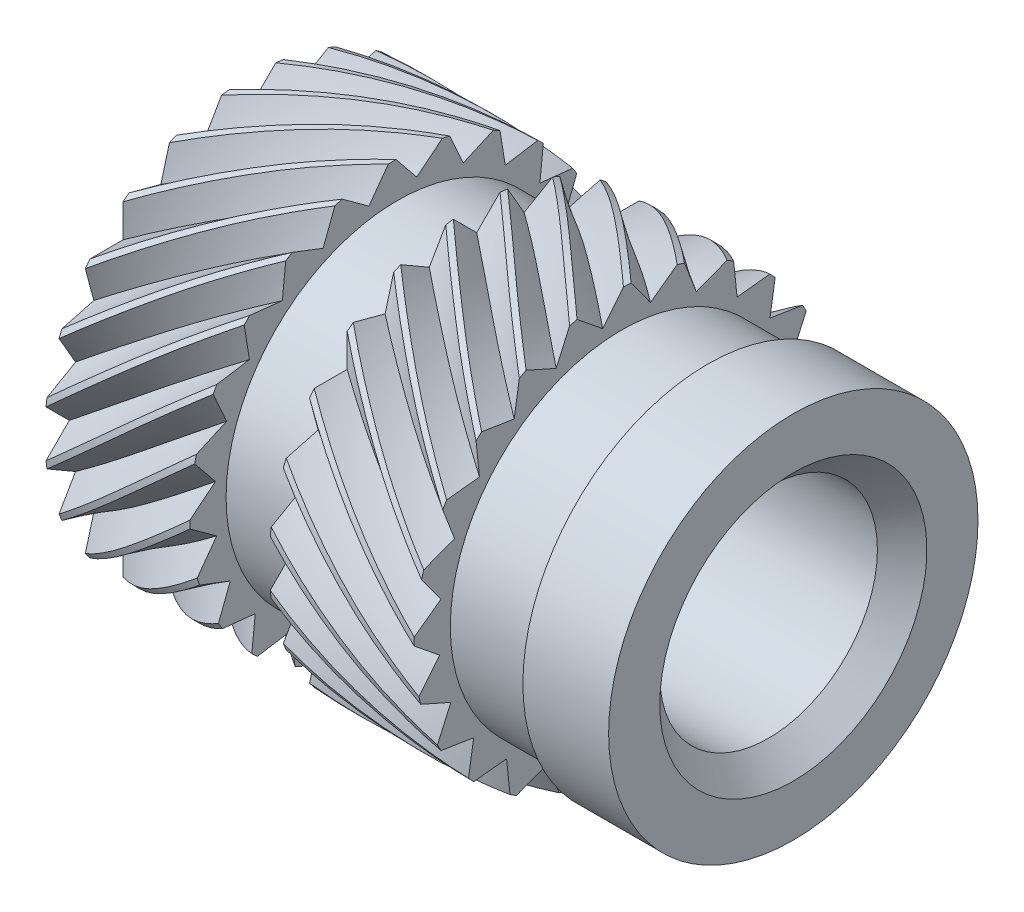
SolidWorks part; units mm, degrees
material "ЛС59-1 ГОСТ 15527-2004"
ref_plane "Front" through (0, 0, 0) normal (0, 0, 1) x (1, 0, 0)
ref_plane "Top" through (0, 0, 0) normal (0, 1, 0) x (1, 0, 0)
ref_plane "Right" through (0, 0, 0) normal (1, 0, 0) x (0, 0, -1)
sketch "Эскиз1" plane through (0, 0, 0) normal (0, 0, 1) x (1, 0, 0)
  line L0 (0, 1.5) -> (0, 3.15)
  line L1 (0, 3.15) -> (2.2, 3.15)
  line L2 (2.2, 3.15) -> (2.2, 2.6)
  line L3 (2.2, 2.6) -> (3.4, 2.6)
  line L4 (3.4, 2.6) -> (3.4, 3.15)
  line L5 (3.4, 3.15) -> (5.6, 3.15)
  line L6 (5.6, 3.15) -> (5.6, 2.6)
  line L7 (5.6, 2.6) -> (6.9, 2.6)
  line L8 (6.9, 2.6) -> (6.9, 2.8)
  line L9 (6.9, 2.8) -> (8.2, 2.8)
  line L10 (8.2, 2.8) -> (8.2, 1.5)
  line L11 (8.2, 1.5) -> (0, 1.5)
  line L12 (0, 0) -> (5.7184, 0) construction
  dimension "D1" = 6.3
  dimension "D2" = 3
  dimension "D3" = 5.2
  dimension "D4" = 5.2
  dimension "D5" = 5.6
  dimension "D6" = 8.2
  dimension "D7" = 1.3
  dimension "D8" = 1.3
  dimension "D9" = 2.2
revolve "Повернуть1" add sketch "Эскиз1" angle 360 about L12
hole_wizard "Отверстие обработанное метчиком M41" positions "Эскиз3" profile "Эскиз2" tap size "M4" standard "Din" end condition through all
sketch "Эскиз3" plane through (0, 0, 0) normal (-1, 0, 0) x (0, 0, 1)
  point P0 (0, 0)
sketch "Эскиз2" plane through (0, 0, 0) normal (0, 1, 0) x (0, 0, 1)
  line L0 (0, 0) -> (0, 8.2)
  line L1 (0, 8.2) -> (2.025, 8.2)
  line L2 (1.65, 7.825) -> (1.65, 0.375)
  line L3 (1.65, 0.375) -> (2.025, 0)
  line L5 (2.025, 0) -> (0, 0)
  line L6 (-1.65, 0.375) -> (-2.025, 0) construction
  line L7 (2.025, 8.2) -> (1.65, 7.825)
  line L8 (-2.025, 8.2) -> (-1.65, 7.825) construction
  line L11 (0, -6.35) -> (0, 107.95) construction
  dimension "Диаметр проходного сверла" = 3.3
  dimension "Глубина проходного сверла" = 8.2
  dimension "Диаметр передней зенковки" = 4.05
  dimension "Угол передней зенковки" = 90
  dimension "Диаметр задней зенковки" = 4.05
  dimension "Угол задней зенковки" = 90
cosmetic thread "Отверстие резьбы1" parameters "D2"=4
sketch "Эскиз4" plane through (0, 0, 0) normal (-1, 0, 0) x (0, 0, 1)
  circle A1 centre (0, 0) radius 3.15
  circle A2 centre (0, 0) radius 3.15
  dimension "D1" = 0
curve "Спираль1" pitch 22 height 2.86 turns 0.13
sketch "Эскиз5" plane through (0, 0, 0) normal (-1, 0, 0) x (0, 0, 1)
  line L0 (3.1301, 0.3536) -> (2.7765, 0)
  line L1 (2.7765, 0) -> (3.1301, -0.3536)
  line L2 (0, 0) -> (2.7765, 0) construction
  circle A0 centre (0, 0) radius 3.15 construction
  arc A1 (3.1301, -0.3536) -> (3.1301, 0.3536) centre (0, 0) ccw
  dimension "D1" = 0.5
sweep "Вырез-По траектории1" cut profiles "Эскиз5" path "Спираль1" align with end faces yes
sketch "Эскиз6" plane through (3.4, 0, 0) normal (-1, 0, 0) x (0, 0, 1)
  circle A1 centre (0, 0) radius 3.15
  circle A2 centre (0, 0) radius 3.15
  dimension "D1" = 0
curve "Спираль2" pitch 22 height 2.86 turns 0.13
sketch "Эскиз7" plane through (3.4, 0, 0) normal (-1, 0, 0) x (0, 0, 1)
  line L2 (3.1301, 0.3536) -> (2.7765, 0)
  line L3 (2.7765, 0) -> (3.1301, -0.3536)
  line L4 (3.1301, 0.3536) -> (2.7765, 0)
  line L5 (2.7765, 0) -> (3.1301, -0.3536)
  arc A1 (3.1301, -0.3536) -> (3.1301, 0.3536) centre (0, 0) ccw
  arc A2 (3.1301, -0.3536) -> (3.1301, 0.3536) centre (0, 0) ccw
  dimension "D1" = 0
sweep "Вырез-По траектории2" cut profiles "Эскиз7" path "Спираль2" align with end faces yes
pattern_circular "Круговой массив1" count 24 over 360 about axis through (0, 0, 0) along (-1, 0, 0) of "Вырез-По траектории1", "Вырез-По траектории2"
